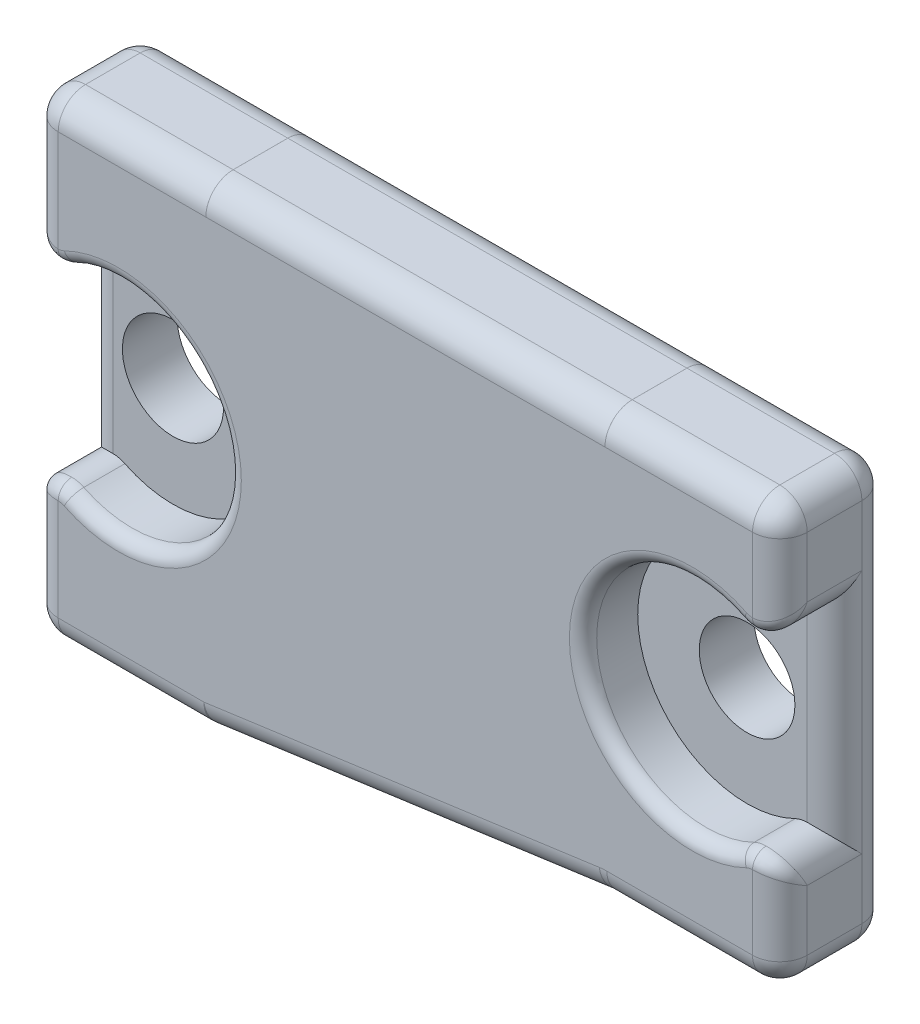
SolidWorks part; units mm, degrees
ref_plane "Front Plane" through (0, 0, 0) normal (0, 0, 1) x (1, 0, 0)
ref_plane "Top Plane" through (0, 0, 0) normal (0, 1, 0) x (1, 0, 0)
ref_plane "Right Plane" through (0, 0, 0) normal (1, 0, 0) x (0, 0, -1)
sketch "Sketch1" plane through (0, 0, 0) normal (0, 0, 1) x (1, 0, 0)
  line L0 (-107.8, -56.6646) -> (-93.2, -56.6493)
  line L1 (-107.8, -74.0646) -> (-93.2, -72.0493)
  line L8 (-86.8, -72.0493) -> (-86.8, -56.6493)
  line L9 (-86.8, -56.6493) -> (-93.2, -56.6493)
  line L11 (-93.2, -72.0493) -> (-86.8, -72.0493)
  line L12 (-114.2, -74.0646) -> (-107.8, -74.0646)
  line L14 (-107.8, -56.6646) -> (-114.2, -56.6646)
  line L15 (-114.2, -56.6646) -> (-114.2, -74.0646)
  circle A0 centre (-111, -65.3646) radius 1.85
  circle A1 centre (-90, -64.3493) radius 1.75
  dimension "D2" = 3.5
  dimension "D1" = 6.4
extrude "Boss-Extrude1" add sketch "Sketch1" along normal blind 4
sketch "Sketch2" plane through (0, 0, 4) normal (0, 0, 1) x (1, 0, 0)
  circle A0 centre (-111, -65.3646) radius 4
  circle A1 centre (-90, -64.3493) radius 4
  dimension "D1" = 8
  dimension "D2" = 8
extrude "Cut-Extrude1" cut sketch "Sketch2" against normal blind 2
fillet "Fillet1" radius 1 32 edges at (-90, -56.6493, 4) (-90, -56.6493, 0) (-93.2, -56.6493, 2) (-100.5, -56.657, 4) (-100.5, -56.657, 0) (-114.2, -67.7646, 3) (-114.2, -70.9146, 4) (-114.2, -65.3646, 0) (-114.2, -59.8146, 4) (-114.2, -62.9646, 3) (-114.2, -65.3646, 2) (-114.2, -74.0646, 2) (-111, -74.0646, 4) (-111, -74.0646, 0) (-107.8, -74.0646, 2) (-100.5, -73.057, 4) (-100.5, -73.057, 0) (-93.2, -72.0493, 2) (-90, -72.0493, 4) (-90, -72.0493, 0) (-86.8, -61.9493, 3) (-86.8, -59.2993, 4) (-86.8, -56.6493, 2) (-86.8, -64.3493, 0) (-86.8, -72.0493, 2) (-86.8, -69.3993, 4) (-86.8, -66.7493, 3) (-86.8, -64.3493, 2) (-107.8, -56.6646, 2) (-111, -56.6646, 4) (-114.2, -56.6646, 2) (-111, -56.6646, 0)
fillet "Fillet2" radius 0.5 10 edges at (-87.0929, -60.5665, 3.7071) (-88.0258, -60.8335, 4) (-87.0929, -68.1322, 3.7071) (-88.0258, -67.8652, 4) (-113.9071, -69.1474, 3.7071) (-112.9742, -68.8804, 4) (-113.9071, -61.5817, 3.7071) (-112.9742, -61.8487, 4) (-94, -64.3493, 4) (-107, -65.3646, 4)
